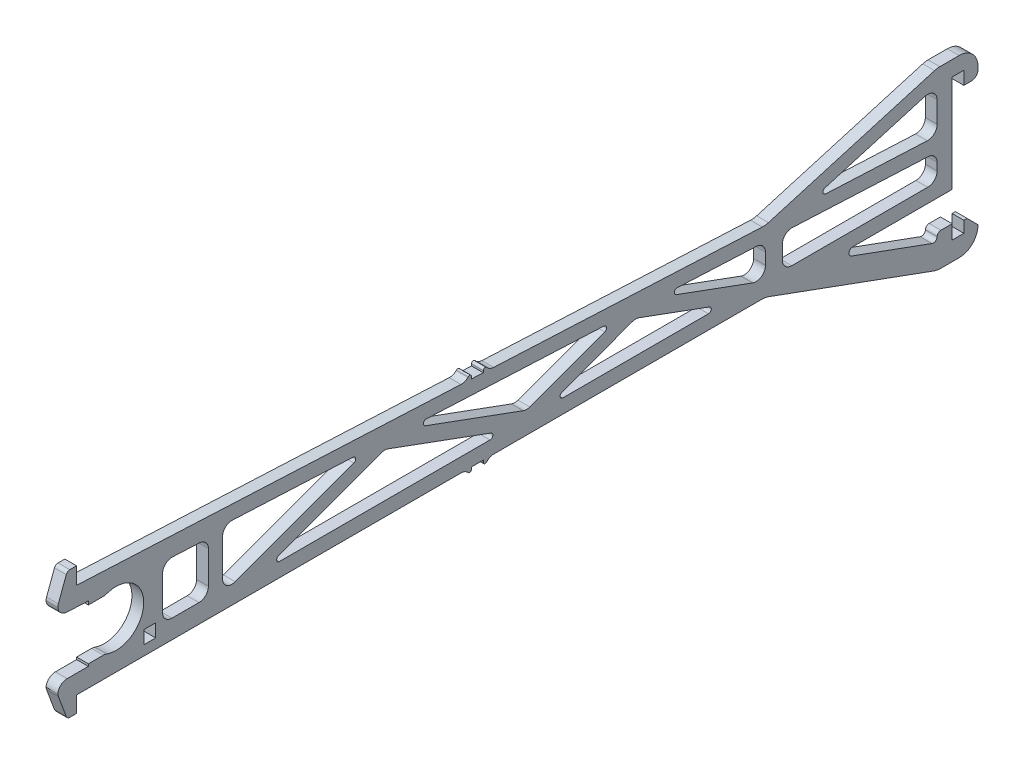
SolidWorks part; units mm, degrees
material "Delrin"
ref_plane "Front Plane" through (0, 0, 0) normal (0, 0, 1) x (1, 0, 0)
ref_plane "Top Plane" through (0, 0, 0) normal (0, 1, 0) x (1, 0, 0)
ref_plane "Right Plane" through (0, 0, 0) normal (1, 0, 0) x (0, 0, -1)
sketch "Sketch1" plane through (0, 0, 0) normal (1, 0, 0) x (0, 0, -1)
  line L0 (0.2976, 6.2667) -> (87.5851, 2.1213)
  line L1 (0, -6.2738) -> (87.5851, -6.2738)
  line L2 (110.744, 8.8955) -> (113.7158, 8.8955)
  line L3 (12.4587, 3.1463) -> (0.1771, 3.7296)
  line L4 (12.4587, -3.7338) -> (0, -3.7338)
  line L5 (-5.3213, -3.7338) -> (-7.8613, -3.7338)
  line L6 (67.8339, 3.0593) -> (67.8339, 1.1543) construction
  line L7 (110.744, -6.2738) -> (110.744, 8.8955) construction
  line L8 (-5.3213, 0.0027) -> (-5.3213, 22.0409) construction
  line L9 (0.2976, 6.2667) -> (-5.3213, 6.5336)
  line L10 (-5.3213, 6.5336) -> (-5.3213, 8.8104)
  line L11 (-5.3213, 8.8104) -> (-7.8613, 8.8104)
  line L12 (-7.8613, 8.8104) -> (-7.8613, 4.1114)
  line L13 (14.3637, 3.6937) -> (14.3637, 5.5987) construction
  line L14 (0, -6.2738) -> (-5.3213, -6.2738)
  line L15 (-5.3213, -6.2738) -> (-5.3213, -8.4328)
  line L16 (14.3637, 3.6937) -> (14.3637, -4.3688)
  line L19 (-5.3213, -8.4328) -> (-7.8613, -8.4328)
  line L20 (-7.8613, -8.4328) -> (-7.8613, -3.7338)
  line L21 (67.8339, -4.3688) -> (67.8339, -6.2738) construction
  line L22 (12.4587, 3.1463) -> (12.4587, -3.7338)
  line L23 (0, 3.7338) -> (0, -3.7338)
  line L24 (115.3668, 5.0855) -> (114.3508, 5.0855)
  line L25 (114.3508, 5.0855) -> (114.3508, 6.8635)
  line L26 (114.3508, 6.8635) -> (112.776, 6.8635)
  line L27 (112.776, 6.8635) -> (112.776, -6.2738)
  line L28 (112.776, -12.1865) -> (114.3508, -12.1865)
  line L29 (114.3508, -12.1865) -> (114.3508, -10.6625)
  line L30 (114.3508, -10.6625) -> (114.7826, -10.6625)
  line L31 (116.2558, -12.1357) -> (116.2558, -12.1865)
  line L32 (113.7158, -14.7265) -> (110.744, -14.7265)
  line L33 (110.744, -14.7265) -> (110.744, -6.2738) construction
  line L34 (116.2558, 5.9745) -> (116.2558, 6.3555)
  line L35 (114.7826, -10.6625) -> (116.2558, -12.1357)
  line L36 (89.8711, 0.1078) -> (89.8711, -4.3688)
  line L37 (87.5851, 0.2163) -> (87.5851, -4.3688)
  line L38 (87.5851, 2.1213) -> (110.744, 8.8955)
  line L39 (93.4228, 1.8441) -> (110.744, 6.9107)
  line L40 (87.5851, -6.2738) -> (110.744, -14.7265)
  line L41 (96.4749, -6.2738) -> (110.744, -11.4818)
  line L42 (88.6301, -3.4106) -> (111.789, -11.8633) construction
  line L43 (88.1199, 0.2929) -> (111.2788, 7.0671) construction
  line L44 (96.4749, -6.2738) -> (110.744, -6.2738)
  line L45 (-1.4689, 3.4327) -> (-3.7338, 3.4327)
  line L46 (93.4228, 1.8441) -> (110.744, 1.0215)
  line L47 (87.5851, -4.8088) -> (87.5851, 49995.1912) construction
  line L48 (110.744, 6.9107) -> (110.744, 1.0215)
  line L49 (110.744, -0.8835) -> (110.744, -4.3688)
  line L50 (112.776, -12.1865) -> (112.776, -10.2815)
  line L51 (110.744, -6.2738) -> (112.776, -6.2738)
  line L52 (112.776, -10.2815) -> (110.744, -10.2815)
  line L53 (110.744, -10.2815) -> (110.744, -11.4818)
  line L56 (14.3637, -4.3688) -> (87.5851, -4.3688)
  line L57 (14.3637, 3.6937) -> (87.5851, 0.2163)
  line L58 (89.8711, 0.1078) -> (110.744, -0.8835)
  line L59 (89.8711, -4.3688) -> (110.744, -4.3688)
  line L60 (-3.7338, 0) -> (-3.7338, 18.3867) construction
  line L61 (-3.7338, 3.9153) -> (-7.8613, 4.1114)
  line L62 (-3.7338, -3.7338) -> (-5.3213, -3.7338)
  line L63 (-3.7338, 3.4327) -> (-3.7338, 3.9153)
  line L64 (-1.4689, -3.4327) -> (-3.7338, -3.4327)
  line L65 (-3.7338, -3.4327) -> (-3.7338, -3.7338)
  line L66 (6.2738, 3.4401) -> (6.2738, -3.7338)
  line L67 (3.7338, 0) -> (3.7338, 11.926) construction
  arc A0 (0, -3.7338) -> (0, 3.7338) centre (0, 0) ccw
  circle A1 centre (0, 0) radius 6.2738 construction
  arc A2 (113.7158, 8.8955) -> (116.2558, 6.3555) centre (113.7158, 6.3555) cw
  arc A3 (116.2558, -12.1865) -> (113.7158, -14.7265) centre (113.7158, -12.1865) cw
  arc A4 (116.2558, 5.9745) -> (115.3668, 5.0855) centre (115.3668, 5.9745) cw
  arc A5 (0, 3.7338) -> (-1.4689, 3.4327) centre (0, 0) ccw
  circle A6 centre (0, 0) radius 3.7338 construction
  arc A7 (-1.4689, -3.4327) -> (0, -3.7338) centre (0, 0) ccw
  point P47 (116.2558, 8.8955)
  point P50 (116.2558, -14.7265)
  point P53 (116.2558, 5.0855)
  point P54 (116.2558, -10.6625)
  point P56 (116.2558, -10.6625)
  point P79 (3.5707, 1.0917)
  dimension "D1" = 7.4676
  dimension "D2" = 2.54
  dimension "D3" = 5.842
  dimension "D8" = 1.5748
  dimension "D18" = 2.54
  dimension "D19" = 2.54
  dimension "D20" = 0.889
  dimension "D5" = 87.5851
  dimension "D10" = 1.905
  dimension "D11" = 1.778
  dimension "D4" = 5.3842
  dimension "D9" = 1.5748
  dimension "D14" = 1.524
  dimension "D15" = 3.81
  dimension "D16" = 4.064
  dimension "D17" = 1.905
  dimension "D22" = 19.05
  dimension "D23" = 20.8729
  dimension "D24" = 2.032
  dimension "D25" = 2.286
  dimension "D29" = 1.905
  dimension "D13" = 2.54
  dimension "D30" = 4.699
  dimension "D31" = 1.905
  dimension "D32" = 17.78
  dimension "D33" = 1.5875
  dimension "D6" = 1.905
  dimension "D7" = 0.4826
  dimension "D34" = 2.54
  dimension "D27" = 3.048
  dimension "D28" = 1.905
extrude "Boss-Extrude1" add sketch "Sketch1" along normal blind 1.5875 contours A1 A0 | A4 L34 A2 L2 L38 L0 L9 L10 L11 L12 L49 L20 L19 L15 L14 L1 L40 L32 A3 L31 L35 L30 L29 L28 L50 L52 L53 L41 L44 L51 L27 L26 L25 L24 | L22 L16 | L37 L36 region at (0, 2.932, -43.8814) region at (0, -0.1374, -4.5101)
sketch "Sketch8" plane through (0, 0, 0) normal (-1, 0, 0) x (0, 0, 1)
  line L0 (-87.5851, -4.3688) -> (-73.2117, 0.8989)
  line L1 (-14.3637, 3.6937) -> (-87.5851, 0.2163) construction
  line L2 (-82.0491, -4.3688) -> (-70.0885, 0.0147)
  line L3 (-70.0885, 0.0147) -> (-58.1279, -4.3688)
  line L4 (-14.3637, -4.3688) -> (-87.5851, -4.3688) construction
  line L5 (-67.6819, 1.1616) -> (-55.3599, -3.3543)
  line L6 (-55.3599, -3.3543) -> (-39.369, 2.5062)
  line L7 (-52.5919, -4.3688) -> (-36.2458, 1.6219)
  line L8 (-14.3637, -4.3688) -> (-33.8392, 2.7688)
  line L9 (-14.3637, 3.6937) -> (-14.3637, -4.3688) construction
  line L10 (-19.8997, -4.3688) -> (-36.2458, 1.6219)
  line L17 (-14.3637, -4.3688) -> (-19.8997, -4.3688)
  line L18 (-33.8392, 2.7688) -> (-39.369, 2.5062)
  line L19 (-82.0491, -4.3688) -> (-87.5851, -4.3688)
  line L20 (-52.5919, -4.3688) -> (-58.1279, -4.3688)
  line L21 (-67.6819, 1.1616) -> (-73.2117, 0.8989)
  point P6 (0, 0)
  dimension "D1" = 1.905
  dimension "D2" = 1.905
  dimension "D3" = 1.905
  dimension "D4" = 1.905
extrude "Boss-Extrude5" add sketch "Sketch8" against normal up to surface (1.5875 mm away) up to face at (1.5875, -2.5084, -67.0694)
sketch "Sketch7" plane through (0, 0, 0) normal (-1, 0, 0) x (0, 0, 1)
  line L0 (6.5913, 8.8104) -> (7.8613, 5.3814)
  line L1 (5.3213, 8.8104) -> (7.8613, 8.8104) construction
  line L2 (7.8613, 8.8104) -> (7.8613, 4.1114) construction
  line L3 (6.5913, 8.8104) -> (7.8613, 8.8104)
  line L4 (7.8613, 8.8104) -> (7.8613, 5.3814)
  line L5 (6.5913, -8.4328) -> (7.8613, -5.0038)
  line L6 (5.3213, -8.4328) -> (7.8613, -8.4328) construction
  line L7 (7.8613, -8.4328) -> (7.8613, -3.7338) construction
  line L8 (6.5913, -8.4328) -> (7.8613, -8.4328)
  line L9 (7.8613, -8.4328) -> (7.8613, -5.0038)
  dimension "D1" = 1.27
  dimension "D2" = 1.27
  dimension "D3" = 1.27
extrude "Cut-Extrude2" cut sketch "Sketch7" against normal through all
fillet "Fillet1" radius 2.54 4 edges at (0.7937, 2.1213, -87.5851) (0.7937, 8.8955, -110.744) (0.7937, -6.2738, -87.5851) (0.7937, -14.7265, -110.744)
fillet "Fillet2" radius 1.27 11 edges at (0.7937, 1.0215, -110.744) (0.7937, 6.9107, -110.744) (0.7937, -4.3688, -89.8711) (0.7937, 0.1078, -89.8711) (0.7937, -4.3688, -110.744) (0.7937, -0.8835, -110.744) (0.7937, 0.2163, -87.5851) (0.7937, -3.7338, -6.2738) (0.7937, 3.4401, -6.2738) (0.7937, -3.7338, -12.4587) (0.7937, 3.1463, -12.4587)
fillet "Fillet3" radius 0.508 2 edges at (0.7937, -6.2738, -96.4749) (0.7937, -11.4818, -110.744)
fillet "Fillet4" radius 0.508 1 edges at (0.7937, -10.2815, -110.744)
sketch "Sketch6" plane through (1.5875, 0, 0) normal (-1, 0, 0) x (0, 0, 1)
  line L0 (-47.0577, -6.2738) -> (-47.9467, -7.1628)
  line L1 (5.3213, 6.5336) -> (-87.16, 2.1415) construction
  line L2 (-47.9467, -17.1193) -> (-47.9467, 10.2613) construction
  line L3 (-47.9467, -7.1628) -> (-47.9467, -6.2738)
  line L4 (-47.9467, -6.2738) -> (-47.0577, -6.2738)
  line L5 (-87.1361, -6.2738) -> (5.3213, -6.2738) construction
  line L6 (-48.7404, -10.0838) -> (-48.7404, 6.4573) construction
  line L7 (-49.5342, -10.0838) -> (-47.9467, -10.0838) construction
  line L8 (-49.5342, -6.2738) -> (-50.4232, -6.2738)
  line L9 (-49.5342, -7.1628) -> (-49.5342, -6.2738)
  line L10 (-50.4232, -6.2738) -> (-49.5342, -7.1628)
  line L11 (-50.4222, 3.8862) -> (-49.5342, 4.8174)
  line L13 (-49.5342, -17.1193) -> (-49.5342, 10.2613) construction
  line L14 (-49.5342, 4.8174) -> (-49.5342, 3.9284)
  line L15 (-49.5342, 3.9284) -> (-50.4222, 3.8862)
  line L16 (-47.9467, 4.0038) -> (-47.0587, 4.046)
  line L17 (-47.0587, 4.046) -> (-47.9467, 4.8928)
  line L18 (-47.9467, 4.8928) -> (-47.9467, 4.0038)
  dimension "D1" = 0.889
extrude "Boss-Extrude3" add sketch "Sketch6" along normal up to surface (1.5875 mm away) contours L4 L3 L0 | L8 L10 L9 | L15 L14 L11 | L17 L18 L16 | L18 L17 L16 | L14 L15 L11 | L10 L8 L9 | L3 L4 L0 region at (1.5875, -6.5701, -47.6504) region at (1.5875, -6.5701, -49.8305) region at (1.5875, 4.2107, -49.8302) region at (1.5875, 4.3142, -47.6507) up to face at (0, -2.3719, -36.2458)
fillet "Fillet5" radius 1.27 4 edges at (0.7937, 3.8862, -50.4222) (0.7937, 4.046, -47.0587) (0.7937, -6.2738, -50.4232) (0.7937, -6.2738, -47.0577)
fillet "Fillet6" radius 0.254 4 edges at (0.7937, -7.1628, -49.5342) (0.7937, -7.1628, -47.9467) (0.7937, 4.8928, -47.9467) (0.7937, 4.8174, -49.5342)
sketch "Sketch5" plane through (1.5875, 0, 0) normal (1, 0, 0) x (0, 0, -1)
  line L8 (3.7592, -4.445) -> (3.7592, -4.953) construction
  line L9 (3.7592, -4.953) -> (5.3467, -4.953) construction
  line L10 (5.3467, -4.953) -> (5.3467, -4.445) construction
  line L11 (5.3467, -4.445) -> (5.3467, -3.683) construction
  line L12 (5.3467, -3.683) -> (5.3467, -3.175) construction
  line L13 (5.3467, -3.175) -> (3.7592, -3.175) construction
  line L14 (3.7592, -3.175) -> (3.7592, -3.683) construction
  line L15 (3.7592, -4.445) -> (3.7592, -3.683) construction
  line L16 (3.7592, -4.445) -> (3.7592, -4.953)
  line L17 (3.7592, -4.953) -> (5.3467, -4.953)
  line L18 (5.3467, -4.953) -> (5.3467, -4.445)
  line L19 (5.3467, -4.445) -> (5.3467, -3.683)
  line L20 (5.3467, -3.683) -> (5.3467, -3.175)
  line L21 (5.3467, -3.175) -> (3.7592, -3.175)
  line L22 (3.7592, -3.175) -> (3.7592, -3.683)
  line L23 (3.7592, -4.445) -> (3.7592, -3.683)
extrude "Cut-Extrude1" cut sketch "Sketch5" against normal up to next
fillet "Fillet9" radius 1.27 2 edges at (0.7937, -3.4327, 1.4689) (0.7937, 3.4327, 1.4689)
fillet "Fillet10" radius 0.381 1 edges at (0.7937, 1.8441, -93.4228)
fillet "Fillet12" radius 1.27 4 edges at (0.7938, -5.0038, 7.8613) (0.7937, -3.7338, 7.8613) (0.7938, 5.3814, 7.8613) (0.7937, 4.1114, 7.8613)
fillet "Fillet13" radius 0.508 2 edges at (0.7938, 8.8104, 6.5913) (0.7938, -8.4328, 6.5913)
fillet "Fillet14" radius 1.27 6 edges at (0.7937, 3.6937, -14.3637) (0.7938, -4.3688, -14.3637) (0.7938, 1.6219, -36.2458) (0.7938, -3.3543, -55.3599) (0.7938, 0.0147, -70.0885) (0.7938, -4.3688, -87.5851)
fillet "Fillet15" radius 0.381 8 edges at (0.7938, -4.3688, -19.8997) (0.7938, -4.3688, -52.5919) (0.7937, 2.7688, -33.8392) (0.7937, 2.5062, -39.369) (0.7937, 1.1616, -67.6819) (0.7937, 0.8989, -73.2117) (0.7938, -4.3688, -58.1279) (0.7938, -4.3688, -82.0491)
